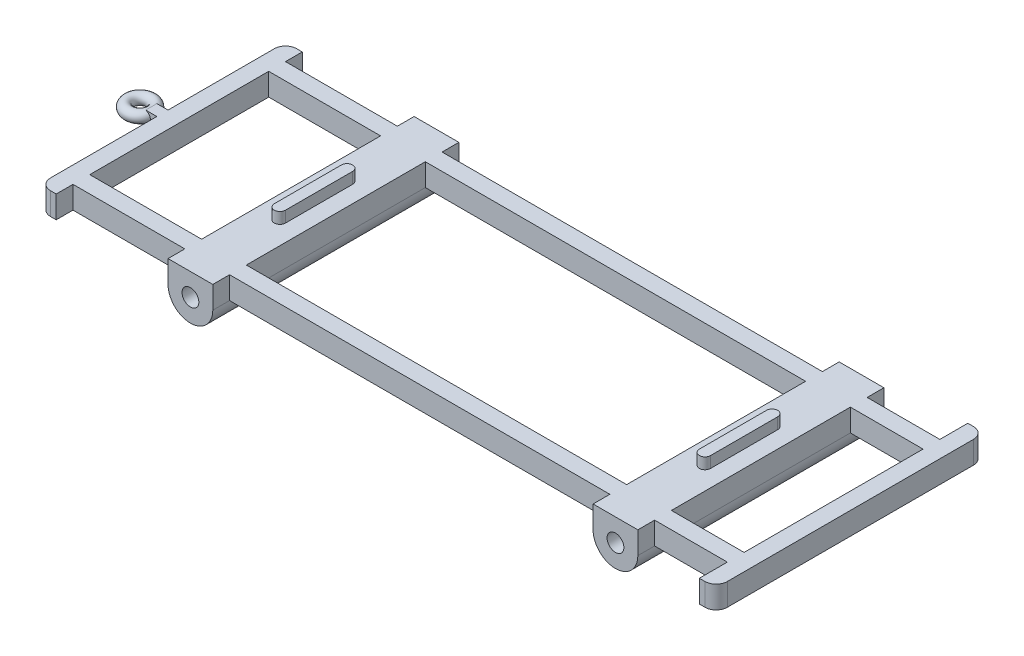
SolidWorks part; units mm, degrees
ref_plane "Ön Düzlem" through (0, 0, 0) normal (0, 0, 1) x (1, 0, 0)
ref_plane "Üst Düzlem" through (0, 0, 0) normal (0, 1, 0) x (1, 0, 0)
ref_plane "Sağ Düzlem" through (0, 0, 0) normal (1, 0, 0) x (0, 0, -1)
sketch "Çizim3" plane through (0, 0, 0) normal (0, 1, 0) x (1, 0, 0)
  line L0 (0, 0) -> (656.7884, 0) construction
  line L1 (15, -80) -> (600, -80)
  line L2 (0, -110) -> (15, -110)
  line L3 (0, -110) -> (0, 110)
  line L4 (0, 110) -> (15, 110)
  line L5 (15, -110) -> (15, 110)
  line L6 (600, 120) -> (615, 120)
  line L7 (600, 120) -> (600, -120)
  line L8 (600, -120) -> (615, -120)
  line L9 (615, 120) -> (615, -120)
  line L10 (15, 95) -> (600, 95)
  line L11 (15, 95) -> (15, 80)
  line L12 (15, 80) -> (600, 80)
  line L13 (600, 95) -> (600, 80)
  line L14 (15, -95) -> (600, -95)
  dimension "D1" = 615
  dimension "D2" = 15
  dimension "D3" = 15
  dimension "D4" = 15
  dimension "D5" = 220
  dimension "D6" = 160
  dimension "D7" = 240
extrude "Yükseklik-Ekstrüzyon1" add sketch "Çizim3" against normal blind 20 contours L5 L14 L7 L1 | L3 L0 L5 L4 | L0 L3 L2 L5 | L0 L7 L8 L9 | L7 L0 L9 L6 | L10 L13 L12 L11 region at (7.5, 0, -55) region at (7.5, 0, 55) region at (607.5, 0, -60) region at (607.5, 0, 60) region at (307.5, 0, 87.5)
sketch "Çizim4" plane through (0, 0, 0) normal (0, 0, 1) x (1, 0, 0)
  line L0 (15, 0) -> (600, 0) construction
  line L1 (115, 0) -> (155, 0)
  line L2 (115, 0) -> (115, -20)
  line L4 (155, 0) -> (155, -20)
  line L5 (15, -20) -> (600, -20) construction
  line L6 (615, -20) -> (615, 0) construction
  line L7 (495, 0) -> (535, 0)
  line L8 (495, 0) -> (495, -20)
  line L10 (535, 0) -> (535, -20)
  line L11 (0, -20) -> (0, 0) construction
  arc A0 (115, -20) -> (155, -20) centre (135, -20) ccw
  arc A1 (495, -20) -> (535, -20) centre (515, -20) ccw
  dimension "D1" = 20
  dimension "D2" = 20
  dimension "D3" = 100
  dimension "D4" = 40
  dimension "D5" = 135
  dimension "D6" = 40
extrude "Yükseklik-Ekstrüzyon2" add sketch "Çizim4" along normal mid plane 220
sketch "Çizim5" plane through (0, 0, 0) normal (0, 0, 1) x (1, 0, 0)
  circle A0 centre (135, -20) radius 7.5
  circle A1 centre (515, -20) radius 7.5
  dimension "D1" = 15
  dimension "D2" = 15
extrude "Kes-Ekstrüzyon1" cut sketch "Çizim5" against normal mid plane 230
sketch "Çizim6" plane through (0, 0, 0) normal (0, 0, 1) x (1, 0, 0)
  line L0 (0, 0) -> (-37.9103, 0) construction
  line L1 (-20, 0) -> (-20, -12.9453) construction
  line L2 (0, -20) -> (0, 0) construction
  circle A0 centre (-30, -5) radius 5
  dimension "D1" = 10
  dimension "D2" = 10
  dimension "D3" = 20
revolve "Döndür1" add sketch "Çizim6" angle 360 about L1
sketch "Çizim7" plane through (0, 0, 0) normal (0, 0, 1) x (1, 0, 0)
  line L0 (0, 0) -> (-10, 0)
  line L1 (-10, 0) -> (0, -20)
  line L2 (0, -20) -> (0, 0)
extrude "Yükseklik-Ekstrüzyon3" add sketch "Çizim7" along normal mid plane 10
fillet "Radyus1" radius 10 4 edges at (615, -10, -120) (615, -10, 120) (0, -10, -110) (0, -10, 110)
sketch "Çizim8" plane through (0, 0, 0) normal (0, 1, 0) x (1, 0, 0)
  line L0 (-10, 0) -> (615, 0) construction
  line L1 (615, 110) -> (615, -110) construction
  line L2 (135, -30) -> (135, 30) construction
  line L3 (130, -30) -> (130, 30)
  line L4 (140, -30) -> (140, 30)
  line L5 (515, -30) -> (515, 30) construction
  line L6 (510, -30) -> (510, 30)
  line L7 (520, -30) -> (520, 30)
  line L8 (0, -100) -> (0, -5) construction
  arc A0 (130, -30) -> (140, -30) centre (135, -30) ccw
  arc A1 (140, 30) -> (130, 30) centre (135, 30) ccw
  arc A2 (510, -30) -> (520, -30) centre (515, -30) ccw
  arc A3 (520, 30) -> (510, 30) centre (515, 30) ccw
  point P7 (135, 0)
  point P13 (515, 0)
  dimension "D2" = 5
  dimension "D4" = 5
  dimension "D1" = 60
  dimension "D3" = 60
  dimension "D5" = 380
  dimension "D6" = 135
extrude "Yükseklik-Ekstrüzyon4" add sketch "Çizim8" along normal blind 10
